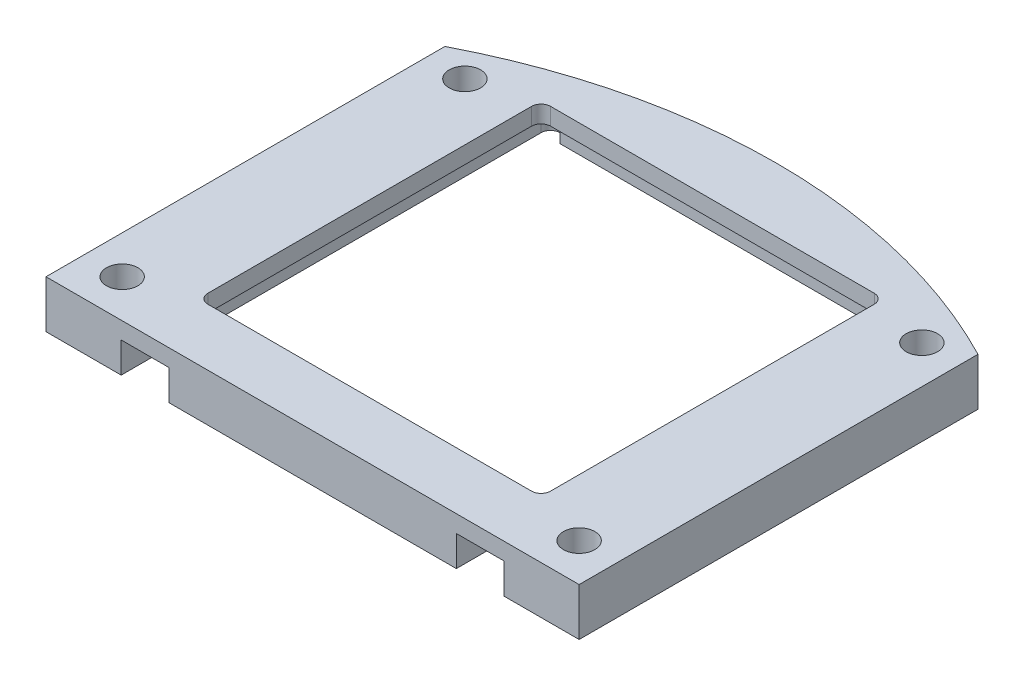
SolidWorks part; units mm, degrees
ref_plane "Front Plane" through (0, 0, 0) normal (0, 0, 1) x (1, 0, 0)
ref_plane "Top Plane" through (0, 0, 0) normal (0, 1, 0) x (1, 0, 0)
ref_plane "Right Plane" through (0, 0, 0) normal (1, 0, 0) x (0, 0, -1)
sketch "Sketch1" plane through (0, 0, 0) normal (0, 1, 0) x (1, 0, 0)
  line L0 (20.1, -20.1) -> (20.1, 21.1)
  line L1 (-20.1, -20.1) -> (20.1, -20.1)
  line L3 (-18.1, 20.1) -> (18.1, 20.1)
  line L5 (-20.1, 21.1) -> (-20.1, -20.1)
  line L7 (-28, -24) -> (28, -24)
  line L8 (-28, -24) -> (-28, 17.8957)
  line L10 (28, -24) -> (28, 17.8957)
  line L15 (-20.1, 21.1) -> (-18.1, 21.1)
  line L16 (-18.1, 20.1) -> (-18.1, 21.1)
  line L19 (20.1, 21.1) -> (18.1, 21.1)
  line L20 (18.1, 20.1) -> (18.1, 21.1)
  circle A0 centre (-24, 16) radius 1.65
  circle A1 centre (24, 16) radius 1.65
  circle A2 centre (-24, -20) radius 1.65
  circle A3 centre (24, -20) radius 1.65
  arc A5 (28.3, 18.0781) -> (-28.3, 18.0781) centre (0, -36.3) ccw construction
  arc A11 (28, 17.8957) -> (-28, 17.8957) centre (0, -36.3) ccw
  point P0 (0, 0)
  point P15 (0, 0)
  dimension "D3" = 16
  dimension "D4" = 20
  dimension "D5" = 20
  dimension "D6" = 16
  dimension "D7" = 24
  dimension "D10" = 24
  dimension "D11" = 3.3
  dimension "D14" = 2
  dimension "D21" = 24
  dimension "D13" = 0.3
  dimension "D2" = 40.2
  dimension "D8" = 24
  dimension "D9" = 24
  dimension "D12" = 28
  dimension "D15" = 1
  dimension "D16" = 2
  dimension "D17" = 1
  dimension "D18" = 20.1
  dimension "D19" = 40.2
  dimension "D20" = 20.1
  dimension "D22" = 28
extrude "Boss-Extrude1" add sketch "Sketch1" along normal blind 5
sketch "Sketch2" plane through (0, 5, 0) normal (0, 1, 0) x (1, 0, 0)
  line L12 (-18, -18) -> (18, -18)
  line L13 (18, -18) -> (18, 18)
  line L14 (-18, 18) -> (-18, -18)
  line L15 (18, 18) -> (-18, 18)
  line L54 (-20.1, 21.1) -> (-20.1, -20.1)
  line L55 (-20.1, -20.1) -> (20.1, -20.1)
  line L56 (20.1, -20.1) -> (20.1, 21.1)
  line L57 (20.1, 21.1) -> (18.1, 21.1)
  line L58 (18.1, 21.1) -> (18.1, 20.1)
  line L59 (18.1, 20.1) -> (-18.1, 20.1)
  line L60 (-18.1, 20.1) -> (-18.1, 21.1)
  line L61 (-18.1, 21.1) -> (-20.1, 21.1)
  line L62 (-20.1, 21.1) -> (-20.1, -20.1)
  line L63 (-20.1, -20.1) -> (20.1, -20.1)
  line L64 (20.1, -20.1) -> (20.1, 21.1)
  line L65 (20.1, 21.1) -> (18.1, 21.1)
  line L66 (18.1, 21.1) -> (18.1, 20.1)
  line L67 (18.1, 20.1) -> (-18.1, 20.1)
  line L68 (-18.1, 20.1) -> (-18.1, 21.1)
  line L69 (-18.1, 21.1) -> (-20.1, 21.1)
  dimension "D1" = 36
  dimension "D3" = 36
  dimension "D4" = 18
  dimension "D5" = 18
  dimension "D6" = 36
  dimension "D7" = 36
  dimension "D2" = 0
extrude "Boss-Extrude2" add sketch "Sketch2" against normal blind 1.8
sketch "Sketch3" plane through (0, 0, 24) normal (0, 0, 1) x (1, 0, 0)
  line L0 (-28, 0) -> (28, 0) construction
  line L1 (-20.1, 0) -> (-15.1, 0)
  line L3 (-20.1, 3.2) -> (-15.1, 3.2)
  line L4 (-15.1, 0) -> (-15.1, 3.2)
  line L5 (20.1, 0) -> (20.1, 3.2)
  line L6 (20.1, 0) -> (15.1, 0)
  line L8 (20.1, 3.2) -> (15.1, 3.2)
  line L9 (15.1, 0) -> (15.1, 3.2)
  line L10 (-20.1, 0) -> (-20.1, 3.2)
  dimension "D1" = 5
  dimension "D2" = 5
  dimension "D3" = 0
  dimension "D4" = 0
  dimension "D5" = 3.2
  dimension "D6" = 3.2
extrude "Cut-Extrude1" cut sketch "Sketch3" against normal up to next
fillet "Fillet1" radius 1 8 edges at (-18, 4.1, 18) (18, 4.1, 18) (18, 4.1, -18) (-18, 4.1, -18) (-20.1, 1.6, -21.1) (-18.1, 1.6, -21.1) (18.1, 1.6, -21.1) (20.1, 1.6, -21.1)
